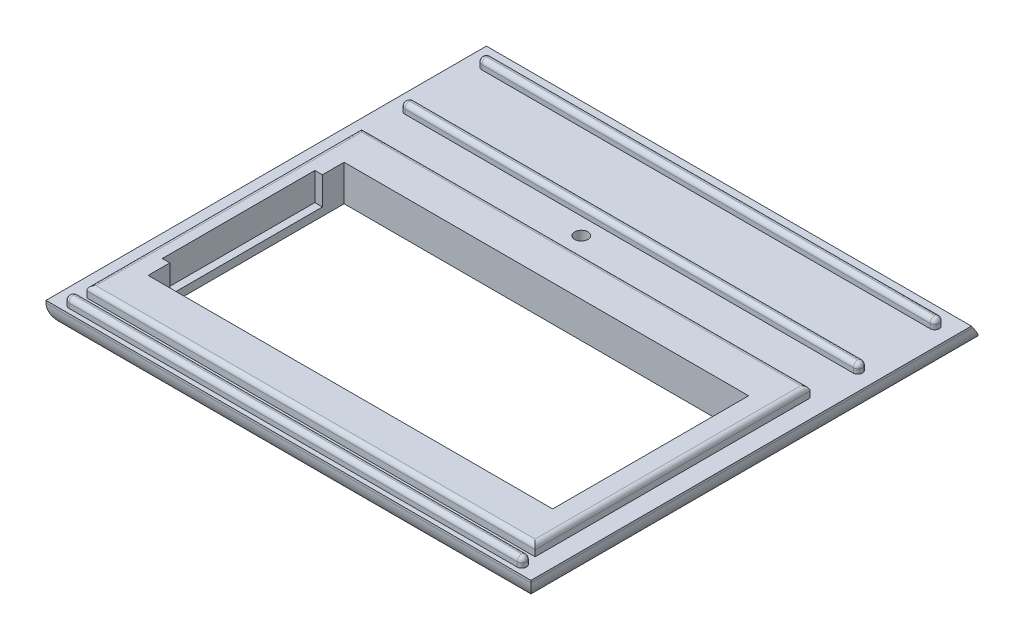
SolidWorks part; units mm, degrees
note: The reader was unsure of these and kept them because the rebuilt part matched: shared geometry of "Sketch1<4>".
ref_plane "Front Plane" through (0, 0, 0) normal (0, 0, 1) x (1, 0, 0)
ref_plane "Top Plane" through (0, 0, 0) normal (0, 1, 0) x (1, 0, 0)
ref_plane "Right Plane" through (0, 0, 0) normal (1, 0, 0) x (0, 0, -1)
sketch "Sketch1" plane through (0, 0, 0) normal (0, 1, 0) x (1, 0, 0)
  line L8 (-28.2204, -35.6927) -> (60.0796, -35.6927)
  line L10 (-28.2204, -35.6927) -> (-28.2204, 7.0873)
  line L12 (-28.2204, 7.0873) -> (60.0796, 7.0873)
  line L14 (60.0796, -35.6927) -> (60.0796, 7.0873)
  line L17 (64.8646, -44.3077) -> (-33.0054, -44.3077)
  line L18 (68.8646, 32.8323) -> (68.8646, -49.2077) construction
  line L19 (68.8646, 32.8323) -> (68.8646, -49.2077)
  line L20 (64.8646, 15.7023) -> (64.8646, -44.3077) construction
  line L21 (64.8646, 15.7023) -> (64.8646, -44.3077)
  line L23 (-33.0054, 15.7023) -> (64.8646, 15.7023)
  line L27 (-33.0054, -44.3077) -> (-33.0054, 15.7023) construction
  line L28 (-33.0054, -44.3077) -> (-33.0054, 15.7023)
  line L29 (-37.0054, -49.2077) -> (68.8646, -49.2077)
  line L30 (68.8646, 32.8323) -> (-37.0054, 32.8323)
  line L32 (-37.0054, -49.2077) -> (-37.0054, 32.8323)
extrude "Boss-Extrude1" add sketch "Sketch1" along normal blind 4
extrude "Boss-Extrude2" add sketch "Sketch1<4>" along a picked direction on the side of the normal offset from surface (6.35 mm away) 2.35
sketch "Sketch1<4>" plane through (0, 0, 0) normal (0, 1, 0) x (1, 0, 0) same geometry as "Sketch1"
sketch "Sketch2" plane through (0, 0, 0) normal (0, -1, 0) x (1, 0, 0)
  circle A1 centre (9.1926, -21.4502) radius 1.4494
extrude "Cut-Extrude1" cut sketch "Sketch2" against normal through all
sketch "Sketch3" plane through (-37.0054, 0, 0) normal (-1, 0, 0) x (0, 0, 1)
  line L0 (-32.8323, 0) -> (-49.7323, 0)
  line L1 (-32.8323, 4) -> (-46.9323, 4)
  line L2 (-46.9323, 4) -> (-49.7323, 0)
  line L3 (-32.8323, 4) -> (-32.8323, 0)
extrude "Boss-Extrude3" add sketch "Sketch3" against normal up to surface (105.87 mm away) up to face at (68.8646, 2, 8.1877)
fillet "Fillet6" radius 1 4 edges at (-33.0054, 6.35, 14.3027) (15.9296, 6.35, -15.7023) (64.8646, 6.35, 14.3027) (15.9296, 6.35, 44.3077)
sketch "Sketch4" plane through (0, 4, 0) normal (0, 1, 0) x (1, 0, 0)
  line L0 (64.8646, 25.1529) -> (-33.0054, 25.1529)
  line L2 (64.8646, 27.1529) -> (-33.0054, 27.1529)
  line L3 (-33.0054, 41.9323) -> (64.8646, 41.9323)
  line L6 (64.8646, -48.2077) -> (-33.0054, -48.2077)
  line L7 (64.8646, -46.2077) -> (-33.0054, -46.2077)
  line L10 (64.8646, 43.9323) -> (-33.0054, 43.9323)
  arc A1 (64.8646, -48.2077) -> (64.8646, -46.2077) centre (64.8646, -47.2077) ccw
  arc A2 (-33.0054, -46.2077) -> (-33.0054, -48.2077) centre (-33.0054, -47.2077) ccw
  arc A3 (64.8646, 25.1529) -> (64.8646, 27.1529) centre (64.8646, 26.1529) ccw
  arc A4 (64.8646, 41.9323) -> (64.8646, 43.9323) centre (64.8646, 42.9323) ccw
  arc A5 (-33.0054, 43.9323) -> (-33.0054, 41.9323) centre (-33.0054, 42.9323) ccw
  arc A6 (-33.0054, 27.1529) -> (-33.0054, 25.1529) centre (-33.0054, 26.1529) ccw
extrude "Boss-Extrude4" add sketch "Sketch4" along normal blind 2
fillet "Fillet7" radius 1 12 edges at (15.9296, 6, 48.2077) (-34.0054, 6, 47.2077) (15.9296, 6, 46.2077) (65.8646, 6, 47.2077) (15.9296, 6, -25.1529) (-34.0054, 6, -26.1529) (15.9296, 6, -27.1529) (65.8646, 6, -26.1529) (15.9296, 6, -43.9323) (65.8646, 6, -42.9323) (15.9296, 6, -41.9323) (-34.0054, 6, -42.9323)
sketch "Sketch5" plane through (0, 6.35, 0) normal (0, 1, 0) x (1, 0, 0)
  line L2 (-28.2204, -30.9527) -> (-28.2204, 2.3473)
  line L3 (-28.2204, -30.9527) -> (-29.8704, -30.9527)
  line L4 (-29.8704, -30.9527) -> (-29.8704, 2.3473)
  line L5 (-29.8704, 2.3473) -> (-28.2204, 2.3473)
extrude "Cut-Extrude3" cut sketch "Sketch5" against normal offset from surface (6.08 mm away) 3.73 up to face at (9.1926, 4, -20.0008)
sketch "Sketch10" plane through (0, 0, 0) normal (0, -1, 0) x (1, 0, 0)
  line L0 (-28.2204, 35.6927) -> (-28.2204, -7.0873) construction
  line L1 (-28.2204, 35.6927) -> (-28.2204, -7.0873)
  line L2 (-28.2204, -7.0873) -> (60.0796, -7.0873) construction
  line L3 (-28.2204, -7.0873) -> (60.0796, -7.0873)
  line L4 (-37.0054, 49.2077) -> (-37.0054, -49.7323)
  line L5 (-37.0054, -49.7323) -> (68.8646, -49.7323)
  line L6 (68.8646, -49.7323) -> (68.8646, 49.2077)
  line L7 (68.8646, 49.2077) -> (-37.0054, 49.2077)
  line L8 (-37.0054, 49.2077) -> (-37.0054, -43.0969)
  line L10 (68.8646, -43.0969) -> (68.8646, 49.2077)
  line L11 (68.8646, 49.2077) -> (-37.0054, 49.2077)
  line L12 (60.0796, 35.6927) -> (60.0796, -7.0873) construction
  line L13 (60.0796, 35.6927) -> (60.0796, -7.0873)
  line L14 (-37.0054, -43.0969) -> (68.8646, -43.0969)
  circle A0 centre (9.1926, -21.4502) radius 1.4494 construction
  circle A1 centre (9.1926, -21.4502) radius 1.4494
  circle M5 centre (9.1926, -21.4502) radius 1.4494
  line M6 (-37.0054, 49.2077) -> (-37.0054, -49.7323)
  line M8 (68.8646, -49.7323) -> (68.8646, 49.2077)
  line M9 (68.8646, 49.2077) -> (-37.0054, 49.2077)
  line M10 (60.0796, 35.6927) -> (60.0796, -7.0873)
  line M11 (60.0796, -7.0873) -> (-28.2204, -7.0873)
  line M12 (-28.2204, -7.0873) -> (-28.2204, 35.6927)
  line M13 (-28.2204, 35.6927) -> (60.0796, 35.6927)
  dimension "D1" = 0
extrude "Boss-Extrude6" add sketch "Sketch10" along normal blind 1.5 contours L14 M6 M8 M9 M13 M10 M11 M12 M5
sketch "Sketch11" plane through (-37.0054, 0, 0) normal (-1, 0, 0) x (0, 0, 1)
  line L2 (-49.7323, 0) -> (-50.7823, -1.5)
  line L4 (-43.0969, -1.5) -> (-50.7823, -1.5)
  line L5 (-43.0969, 0) -> (-49.7323, 0) construction
  line L6 (-43.0969, -1.5) -> (-43.0969, 0) construction
  line L7 (-43.0969, 0) -> (-49.7323, 0)
  line L8 (-43.0969, -1.5) -> (-43.0969, 0)
extrude "Boss-Extrude7" add sketch "Sketch11" against normal up to surface (105.87 mm away) up to face at (68.8646, 0.8333, -14.0738)
fillet "Fillet9" radius 1 1 edges at (9.1926, -1.5, -22.8996)
fillet "Fillet10" radius 5 3 edges at (-37.0054, -1.5, -0.7873) (68.8646, -1.5, -0.7873) (15.9296, -1.5, 49.2077)
